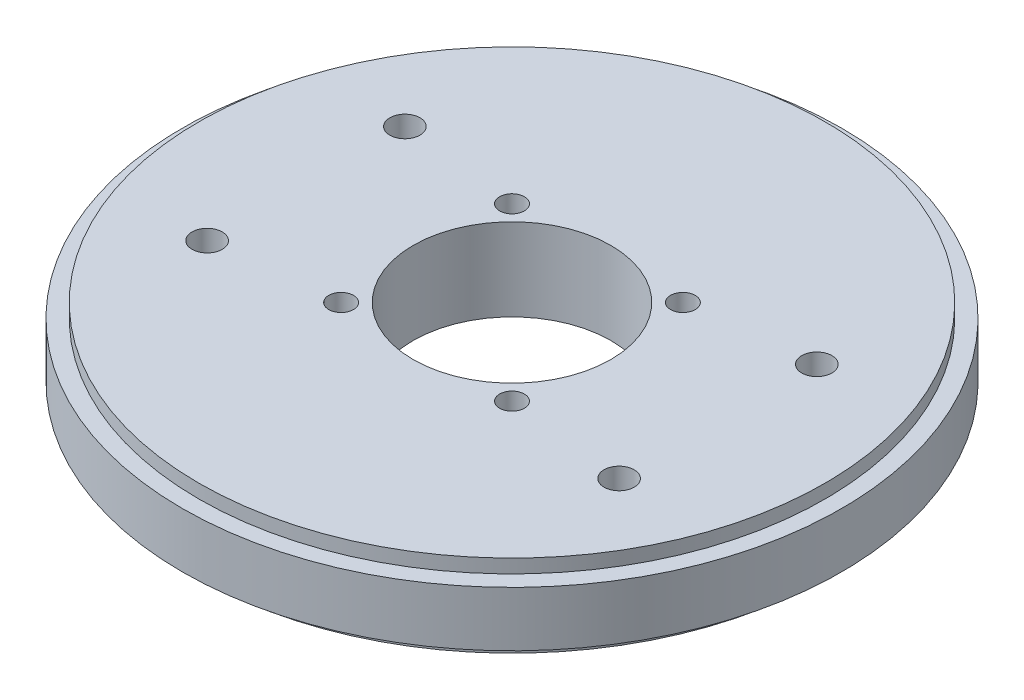
SolidWorks part; units mm, degrees
ref_plane "Front Plane" through (0, 0, 0) normal (0, 0, 1) x (1, 0, 0)
ref_plane "Top Plane" through (0, 0, 0) normal (0, 1, 0) x (1, 0, 0)
ref_plane "Right Plane" through (0, 0, 0) normal (1, 0, 0) x (0, 0, -1)
sketch "Sketch1" plane through (0, 0, 0) normal (0, 1, 0) x (1, 0, 0)
  circle A0 centre (0, 0) radius 57
  circle A1 centre (0, 0) radius 60
  dimension "D1" = 120
  dimension "D2" = 114
extrude "Extrude4" add sketch "Sketch1" along normal mid plane 15 contours A0
extrude "Extrude5" add sketch "Sketch" along normal mid plane 10
sketch "Sketch" plane through (0, 0, 0) normal (0, 1, 0) x (1, 0, 0) same geometry as "Sketch1"
sketch "Sketch5" plane through (0, 0, 0) normal (0, 1, 0) x (1, 0, 0)
  circle A0 centre (0, 0) radius 18
  dimension "D1" = 36
extrude "Extrude6" cut sketch "Sketch5" against normal through all both and the other way through all
hole_wizard "Ø4.5 (4.5) Diameter Hole1" positions "Sketch10" profile "Sketch11" hole size "Ø4.5" standard "ISO" end condition through all
sketch "Sketch10" plane through (0, -7.5, 0) normal (0, -1, 0) x (-1, 0, 0)
  point P6 (15.5563, 15.5563)
sketch "Sketch11" plane through (-15.5563, -7.5, -15.5563) normal (1, 0, 0) x (0, 0, -1)
  line L0 (0, 0) -> (0, 15)
  line L1 (0, 15) -> (2.25, 15)
  line L2 (2.25, 15) -> (2.25, 0)
  line L5 (2.25, 0) -> (0, 0)
  line L11 (0, -6.35) -> (0, 107.95) construction
  dimension "Thru Hole Dia." = 4.5
  dimension "Thru Hole Depth" = 15
ref_axis "Axis1" through (0, -8.25, 0) along (0, 1, 0)
pattern_circular "CirPattern1" count 4 over 360 about axis through (0, -8.25, 0) along (0, 1, 0) of "Ø4.5 (4.5) Diameter Hole1"
hole_wizard "M5 Clearance Hole1" positions "Sketch14" profile "Sketch15" hole size "M5" standard "ISO" end condition through all
sketch "Sketch14" plane through (0, 7.5, 0) normal (0, 1, 0) x (1, 0, 0)
  point P0 (-37.5, 18)
  point P3 (-37.5, -18)
  point P6 (37.5, -18)
  point P9 (37.5, 18)
sketch "Sketch15" plane through (-37.5, 7.5, -18) normal (1, 0, 0) x (0, 0, 1)
  line L0 (0, 0) -> (0, 15)
  line L1 (0, 15) -> (2.75, 15)
  line L2 (2.75, 15) -> (2.75, 0)
  line L5 (2.75, 0) -> (0, 0)
  line L11 (0, -6.35) -> (0, 107.95) construction
  dimension "Thru Hole Dia." = 5.5
  dimension "Thru Hole Depth" = 15
